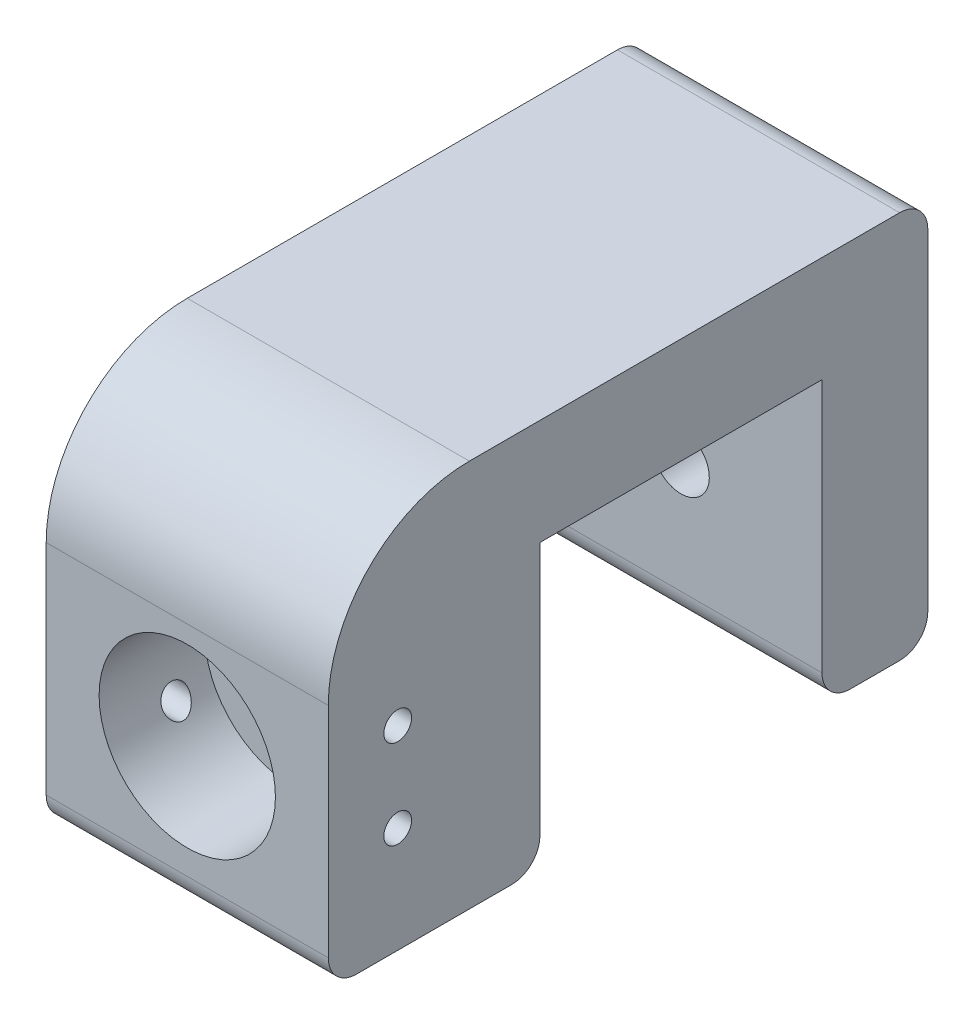
SolidWorks part; units mm, degrees
material "PET"
ref_plane "Front" through (0, 0, 0) normal (0, 0, 1) x (1, 0, 0)
ref_plane "Top" through (0, 0, 0) normal (0, 1, 0) x (1, 0, 0)
ref_plane "Right" through (0, 0, 0) normal (1, 0, 0) x (0, 0, -1)
sketch "Sketch1" plane through (0, 0, 0) normal (1, 0, 0) x (0, 0, -1)
  line L0 (0, 0) -> (0, -25.4)
  line L1 (0, -25.4) -> (-19.05, -25.4)
  line L2 (-19.05, -25.4) -> (-19.05, -3.175)
  line L3 (-6.35, 9.525) -> (34.925, 9.525)
  line L4 (34.925, 9.525) -> (34.925, -25.4)
  line L5 (34.925, -25.4) -> (25.4, -25.4)
  line L6 (25.4, -25.4) -> (25.4, 0)
  line L7 (25.4, 0) -> (0, 0)
  arc A0 (-19.05, -3.175) -> (-6.35, 9.525) centre (-6.35, -3.175) cw
  dimension "D6" = 12.7
  dimension "D1" = 25.4
  dimension "D2" = 25.4
  dimension "D3" = 9.525
  dimension "D4" = 9.525
  dimension "D5" = 19.05
extrude "Boss-Extrude1" add sketch "Sketch1" along normal blind 25.4
sketch "Sketch4" plane through (0, 0, 0) normal (0, 0, -1) x (-1, 0, 0)
  line L0 (-25.4, 0) -> (0, -25.4) construction
  point P0 (-12.7, -12.7)
  point P9 (0, 0)
hole_wizard "1/4 (0.2500) Dowel Hole1" positions "Sketch4" profile "Sketch3" hole size "1/4" standard "ANSI Inch" end condition through all
sketch "Sketch3" plane through (12.7, -12.7, 0) normal (1, 0, 0) x (0, 1, 0)
  line L0 (0, 0) -> (0, 19.05)
  line L1 (0, 19.05) -> (3.175, 19.05)
  line L2 (3.175, 19.05) -> (3.175, 0)
  line L5 (3.175, 0) -> (0, 0)
  line L11 (0, -6.35) -> (0, 107.95) construction
  dimension "Thru Hole Dia." = 6.35
  dimension "Thru Hole Depth" = 19.05
sketch "Sketch7" plane through (0, 0, -34.925) normal (0, 0, -1) x (-1, 0, 0)
  circle A0 centre (-12.7, -12.7) radius 3.175 construction
  point P0 (-12.7, -12.7)
hole_wizard "#10 Clearance Hole1" positions "Sketch7" profile "Sketch6" hole size "#10" standard "ANSI Inch" end condition through all
sketch "Sketch6" plane through (12.7, -12.7, -34.925) normal (1, 0, 0) x (0, 1, 0)
  line L0 (0, 0) -> (0, 53.975)
  line L1 (0, 53.975) -> (2.5527, 53.975)
  line L2 (2.5527, 53.975) -> (2.5527, 0)
  line L5 (2.5527, 0) -> (0, 0)
  line L11 (0, -6.35) -> (0, 107.95) construction
  dimension "Thru Hole Dia." = 5.1054
  dimension "Thru Hole Depth" = 53.975
sketch "Sketch8" plane through (0, 0, 19.05) normal (0, 0, 1) x (1, 0, 0)
  circle A0 centre (12.7, -12.7) radius 7.9375
  dimension "D1" = 15.875
extrude "Cut-Extrude1" cut sketch "Sketch8" against normal offset from surface (9.525 mm away) 9.525 up to face at (12.7, -9.525, 0)
sketch "Sketch11" plane through (25.4, 0, 0) normal (1, 0, 0) x (0, 0, -1)
  line L4 (-19.05, -25.4) -> (0, -25.4) construction
  line L5 (0, -25.4) -> (0, 0) construction
  point P0 (-12.8016, -7.875)
  point P2 (-12.8016, -15.875)
  dimension "D1" = 8
  dimension "D2" = 9.525
  dimension "D3" = 12.8016
hole_wizard "M3x0.5 Tapped Hole1" positions "Sketch11" profile "Sketch10" tap size "M3x0.5" standard "ANSI Metric" end condition through all
sketch "Sketch10" plane through (25.4, -7.875, 12.8016) normal (0, 1, 0) x (0, 0, -1)
  line L0 (0, 0) -> (0, 25.4)
  line L1 (0, 25.4) -> (1.25, 25.4)
  line L2 (1.25, 25.4) -> (1.25, 0)
  line L5 (1.25, 0) -> (0, 0)
  line L11 (0, -6.35) -> (0, 107.95) construction
  dimension "Thru Tap Drill Dia." = 2.5
  dimension "Thru Tap Drill Depth" = 25.4
cosmetic thread "Hole Thread1" parameters "D2"=3
cosmetic thread "Hole Thread2" parameters "D2"=3
fillet "Fillet1" radius 2.54 5 edges at (12.7, 9.525, -34.925) (12.7, -25.4, -34.925) (12.7, -25.4, -25.4) (12.7, -25.4, 0) (12.7, -25.4, 19.05)
